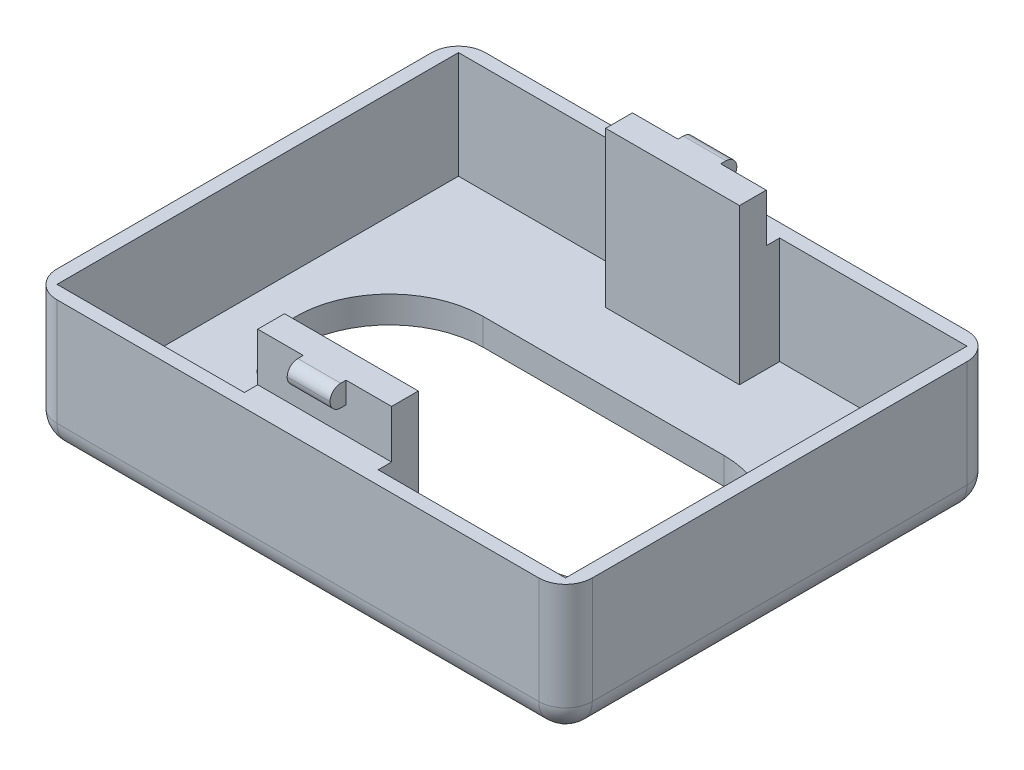
SolidWorks part; units mm, degrees
ref_plane "Front Plane" through (0, 0, 0) normal (0, 0, 1) x (1, 0, 0)
ref_plane "Top Plane" through (0, 0, 0) normal (0, 1, 0) x (1, 0, 0)
ref_plane "Right Plane" through (0, 0, 0) normal (1, 0, 0) x (0, 0, -1)
sketch "Sketch1" plane through (0, 0, 0) normal (0, 1, 0) x (1, 0, 0)
  line L1 (0, 0) -> (100, 0)
  line L2 (0, 0) -> (0, 80)
  line L3 (0, 80) -> (100, 80)
  line L4 (100, 0) -> (100, 80)
  dimension "D1" = 100
  dimension "D2" = 80
extrude "Boss-Extrude1" add sketch "Sketch1" along normal blind 5
sketch "Sketch2" plane through (0, 5, 0) normal (0, 1, 0) x (1, 0, 0)
  line L0 (2.5, 77.5) -> (2.5, 2.5)
  line L1 (0, 80) -> (100, 80)
  line L2 (0, 80) -> (0, 0)
  line L3 (0, 0) -> (100, 0)
  line L4 (100, 80) -> (100, 0)
  line L5 (2.5, 2.5) -> (97.5, 2.5)
  line L6 (97.5, 77.5) -> (97.5, 2.5)
  line L7 (2.5, 77.5) -> (97.5, 77.5)
  dimension "D1" = 2.5
extrude "Boss-Extrude2" add sketch "Sketch2" along normal blind 20
ref_plane "Plane1" through (50, 0, 0) normal (1, 0, 0) x (0, 0, -1)
ref_plane "Plane2" through (0, 0, -40) normal (0, 0, 1) x (1, 0, 0)
sketch "Sketch3" plane through (0, 5, 0) normal (0, 1, 0) x (1, 0, 0)
  line L0 (97.5, 77.5) -> (2.5, 77.5) construction
  line L1 (37.5, 77.5) -> (62.5, 77.5)
  line L2 (37.5, 77.5) -> (37.5, 70)
  line L3 (37.5, 70) -> (62.5, 70)
  line L4 (62.5, 77.5) -> (62.5, 70)
  line L6 (50, -13.75) -> (50, 13.75) construction
  dimension "D1" = 25
  dimension "D2" = 12.5
  dimension "D3" = 7.5
extrude "Boss-Extrude3" add sketch "Sketch3" along normal up to surface (20 mm away) up to face at (50, 25, -40)
sketch "Sketch4" plane through (0, 25, 0) normal (0, 1, 0) x (1, 0, 0)
  line L1 (37.5, 70) -> (62.5, 70)
  line L2 (37.5, 70) -> (37.5, 75)
  line L3 (37.5, 75) -> (62.5, 75)
  line L4 (62.5, 70) -> (62.5, 75)
  line L5 (100, 80) -> (0, 80) construction
  dimension "D1" = 5
extrude "Boss-Extrude4" add sketch "Sketch4" along normal blind 9
sketch "Sketch5" plane through (0, 0, -75) normal (0, 0, -1) x (-1, 0, 0)
  line L6 (-62.5, 34) -> (-37.5, 34) construction
  line L7 (-54, 34) -> (-46, 34)
  line L8 (-54, 34) -> (-54, 30)
  line L9 (-54, 30) -> (-46, 30)
  line L10 (-46, 34) -> (-46, 30)
  point P6 (-50, 34)
  point P7 (-50, 34)
  dimension "D1" = 8
  dimension "D2" = 4
extrude "Boss-Extrude5" add sketch "Sketch5" along normal blind 3
fillet "Fillet1" radius 2 2 edges at (50, 30, -78) (50, 34, -78)
fillet "Fillet2" radius 5 8 edges at (50, 0, 0) (0, 12.5, 0) (0, 0, -40) (0, 12.5, -80) (50, 0, -80) (100, 0, -40) (100, 12.5, 0) (100, 12.5, -80)
mirror "Mirror2" about plane through (0, 0, -40) normal (0, 0, 1) of "Fillet1", "Boss-Extrude5", "Boss-Extrude4", "Boss-Extrude3"
sketch "Sketch6" plane through (0, 5, 0) normal (0, 1, 0) x (1, 0, 0)
  line L0 (50, -11) -> (50, 11) construction
  line L1 (27.5, 57.1204) -> (72.5, 57.1204)
  line L2 (27.5, 22.1204) -> (72.5, 22.1204)
  arc A0 (27.5, 57.1204) -> (27.5, 22.1204) centre (27.5, 39.6204) ccw
  arc A1 (72.5, 22.1204) -> (72.5, 57.1204) centre (72.5, 39.6204) ccw
  dimension "D1" = 35
  dimension "D2" = 35
  dimension "D3" = 22.5
  dimension "D4" = 22.5
extrude "Cut-Extrude1" cut sketch "Sketch6" against normal through all
